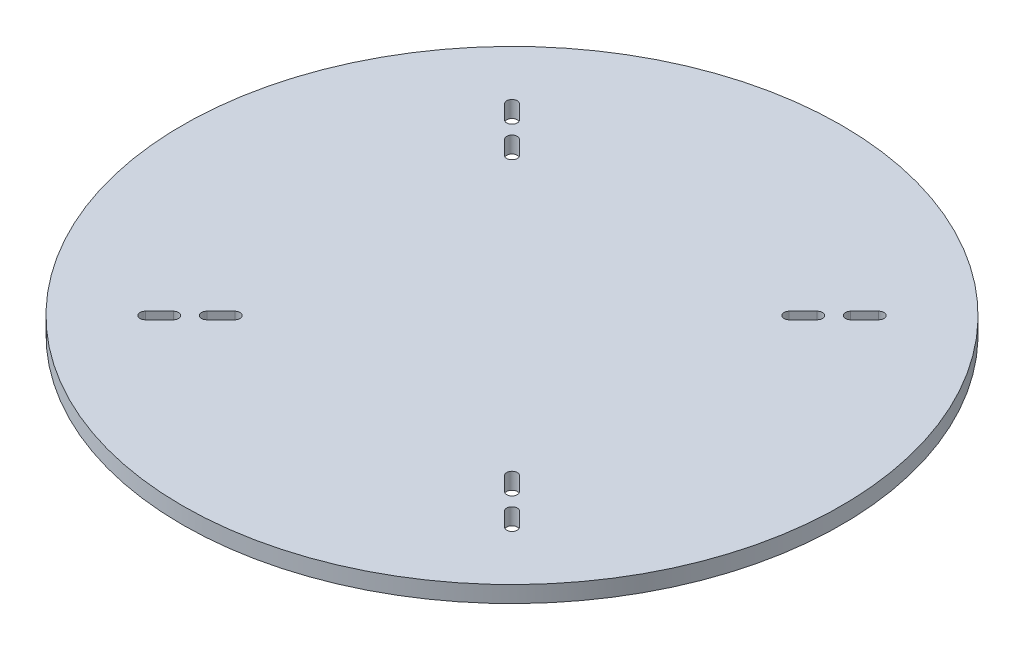
SolidWorks part; units mm, degrees
ref_plane "Front Plane" through (0, 0, 0) normal (0, 0, 1) x (1, 0, 0)
ref_plane "Top Plane" through (0, 0, 0) normal (0, 1, 0) x (1, 0, 0)
ref_plane "Right Plane" through (0, 0, 0) normal (1, 0, 0) x (0, 0, -1)
sketch "Sketch1" plane through (0, 0, 0) normal (0, 1, 0) x (1, 0, 0)
  circle A0 centre (0, 0) radius 127
  point P0 (0, 0)
  dimension "D1" = 254
extrude "Boss-Extrude1" add sketch "Sketch1" along normal blind 6.35
sketch "Sketch2" plane through (0, 6.35, 0) normal (0, 1, 0) x (1, 0, 0)
  line L0 (-71.5526, 80.5329) -> (-80.5329, 71.5526)
  line L1 (-80.5329, 71.5526) -> (-50, 41.0197)
  line L2 (-50, 41.0197) -> (-41.0197, 50)
  line L3 (-41.0197, 50) -> (-71.5526, 80.5329)
  line L4 (0, 127) -> (0, -127) construction
  line L7 (-127, 0) -> (127, 0) construction
  line L10 (-89.8026, 89.8026) -> (0, 0) construction
  line L11 (-70.6546, 70.6546) -> (-65.2664, 65.2664) construction
  line L12 (-69.2177, 72.0914) -> (-63.8296, 66.7033)
  line L13 (-72.0914, 69.2177) -> (-66.7033, 63.8296)
  line L14 (-58.8007, 58.8007) -> (-53.4125, 53.4125) construction
  line L15 (-57.3638, 60.2375) -> (-51.9757, 54.8493)
  line L16 (-60.2375, 57.3638) -> (-54.8493, 51.9757)
  line L17 (-50, 41.0197) -> (-50, 50)
  line L18 (-50, 50) -> (-41.0197, 50)
  line L19 (58.8007, 58.8007) -> (53.4125, 53.4125) construction
  line L20 (57.3638, 60.2375) -> (51.9757, 54.8493)
  line L21 (60.2375, 57.3638) -> (54.8493, 51.9757)
  line L22 (50, 50) -> (41.0197, 50)
  line L23 (50, 41.0197) -> (50, 50)
  line L24 (70.6546, 70.6546) -> (65.2664, 65.2664) construction
  line L25 (69.2177, 72.0914) -> (63.8296, 66.7033)
  line L26 (72.0914, 69.2177) -> (66.7033, 63.8296)
  line L27 (50, 41.0197) -> (41.0197, 50)
  line L28 (80.5329, 71.5526) -> (50, 41.0197)
  line L29 (71.5526, 80.5329) -> (80.5329, 71.5526)
  line L30 (41.0197, 50) -> (71.5526, 80.5329)
  line L31 (70.6546, -70.6546) -> (65.2664, -65.2664) construction
  line L32 (69.2177, -72.0914) -> (63.8296, -66.7033)
  line L33 (72.0914, -69.2177) -> (66.7033, -63.8296)
  line L34 (58.8007, -58.8007) -> (53.4125, -53.4125) construction
  line L35 (57.3638, -60.2375) -> (51.9757, -54.8493)
  line L36 (60.2375, -57.3638) -> (54.8493, -51.9757)
  line L37 (71.5526, -80.5329) -> (80.5329, -71.5526)
  line L38 (80.5329, -71.5526) -> (50, -41.0197)
  line L39 (41.0197, -50) -> (71.5526, -80.5329)
  line L40 (50, -41.0197) -> (50, -50)
  line L41 (50, -41.0197) -> (41.0197, -50)
  line L42 (50, -50) -> (41.0197, -50)
  line L43 (-50, -50) -> (-41.0197, -50)
  line L44 (-50, -41.0197) -> (-50, -50)
  line L45 (-58.8007, -58.8007) -> (-53.4125, -53.4125) construction
  line L46 (-57.3638, -60.2375) -> (-51.9757, -54.8493)
  line L47 (-60.2375, -57.3638) -> (-54.8493, -51.9757)
  line L48 (-70.6546, -70.6546) -> (-65.2664, -65.2664) construction
  line L49 (-69.2177, -72.0914) -> (-63.8296, -66.7033)
  line L50 (-72.0914, -69.2177) -> (-66.7033, -63.8296)
  line L51 (-50, -41.0197) -> (-41.0197, -50)
  line L52 (-80.5329, -71.5526) -> (-50, -41.0197)
  line L53 (-71.5526, -80.5329) -> (-80.5329, -71.5526)
  line L54 (-41.0197, -50) -> (-71.5526, -80.5329)
  arc A0 (-69.2177, 72.0914) -> (-72.0914, 69.2177) centre (-70.6546, 70.6546) ccw
  arc A1 (-66.7033, 63.8296) -> (-63.8296, 66.7033) centre (-65.2664, 65.2664) ccw
  arc A2 (-57.3638, 60.2375) -> (-60.2375, 57.3638) centre (-58.8007, 58.8007) ccw
  arc A3 (-54.8493, 51.9757) -> (-51.9757, 54.8493) centre (-53.4125, 53.4125) ccw
  arc A4 (57.3638, 60.2375) -> (60.2375, 57.3638) centre (58.8007, 58.8007) cw
  arc A5 (54.8493, 51.9757) -> (51.9757, 54.8493) centre (53.4125, 53.4125) cw
  arc A6 (69.2177, 72.0914) -> (72.0914, 69.2177) centre (70.6546, 70.6546) cw
  arc A7 (66.7033, 63.8296) -> (63.8296, 66.7033) centre (65.2664, 65.2664) cw
  arc A8 (69.2177, -72.0914) -> (72.0914, -69.2177) centre (70.6546, -70.6546) ccw
  arc A9 (66.7033, -63.8296) -> (63.8296, -66.7033) centre (65.2664, -65.2664) ccw
  arc A10 (57.3638, -60.2375) -> (60.2375, -57.3638) centre (58.8007, -58.8007) ccw
  arc A11 (54.8493, -51.9757) -> (51.9757, -54.8493) centre (53.4125, -53.4125) ccw
  arc A12 (-57.3638, -60.2375) -> (-60.2375, -57.3638) centre (-58.8007, -58.8007) cw
  arc A13 (-54.8493, -51.9757) -> (-51.9757, -54.8493) centre (-53.4125, -53.4125) cw
  arc A14 (-69.2177, -72.0914) -> (-72.0914, -69.2177) centre (-70.6546, -70.6546) cw
  arc A15 (-66.7033, -63.8296) -> (-63.8296, -66.7033) centre (-65.2664, -65.2664) cw
  circle A16 centre (0, 0) radius 127 construction
  point P19 (-76.0427, 76.0427)
  point P22 (-67.9605, 67.9605)
  point P27 (-56.1066, 56.1066)
  point P35 (-63.8296, 63.8296)
  point P36 (-60.2375, 60.2375)
  point P44 (56.1066, 56.1066)
  point P54 (67.9605, 67.9605)
  point P63 (67.9605, -67.9605)
  point P70 (56.1066, -56.1066)
  point P85 (-56.1066, -56.1066)
  point P92 (-67.9605, -67.9605)
  dimension "D4" = 2.032
  dimension "D5" = 5.08
  dimension "D1" = 43.18
  dimension "D2" = 12.7
  dimension "D3" = 7.62
  dimension "D6" = 4.826
  dimension "D7" = 50
extrude "Cut-Extrude1" cut sketch "Sketch2" against normal through all contours L16 A3 L15 A2 | A5 L21 A4 L20 | A7 L26 A6 L25 | L36 A11 L35 A10 | L33 A9 L32 A8 | A13 L47 A12 L46 | A15 L50 A14 L49 | L12 A1 L13 A0 region at (-56.1066, 6.35, -56.1066) region at (56.1066, 6.35, -56.1066) region at (67.9605, 6.35, -67.9605) region at (67.9605, 6.35, 67.9605) region at (56.1066, 6.35, 56.1066) region at (-56.1066, 6.35, 56.1066) region at (-67.9605, 6.35, 67.9605)
sketch "Sketch3" plane through (0, 0, 0) normal (0, 1, 0) x (1, 0, 0)
  line L0 (0, 0) -> (0, 89.8026) construction
  line L1 (-89.8026, 89.8026) -> (89.8026, 89.8026)
  line L2 (-89.8026, 89.8026) -> (-89.8026, -89.8026)
  line L3 (-89.8026, -89.8026) -> (89.8026, -89.8026)
  line L4 (89.8026, 89.8026) -> (89.8026, -89.8026)
  circle A0 centre (0, 0) radius 127 construction
  circle A1 centre (0, 0) radius 127 construction
  circle A2 centre (0, 0) radius 127
  point P9 (0, 0)
